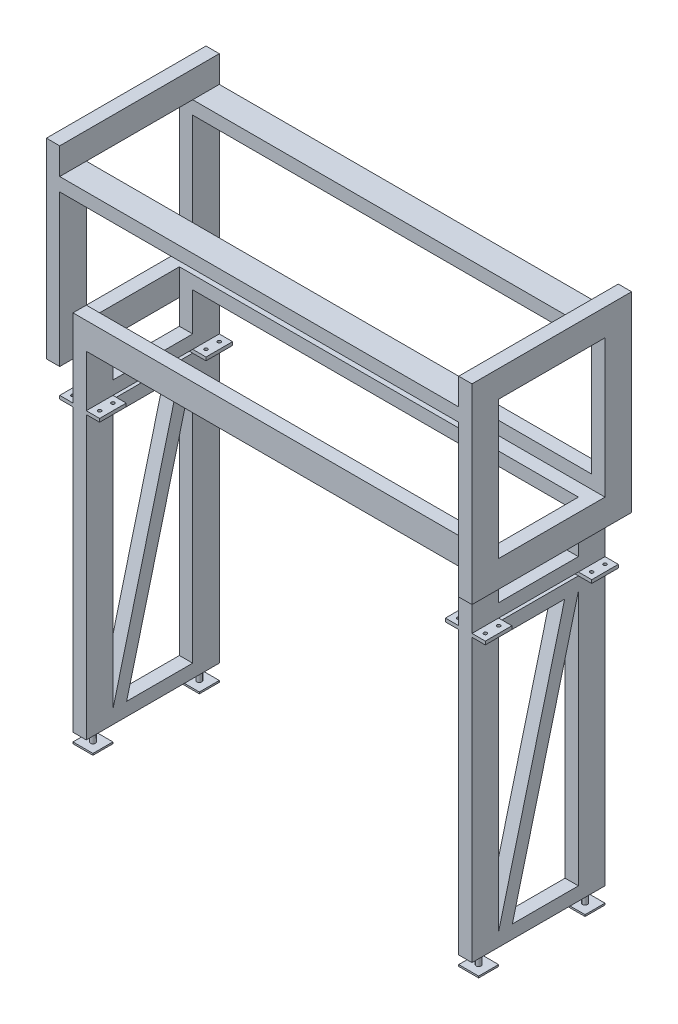
SolidWorks part; units mm, degrees
ref_plane "Front Plane" through (0, 0, 0) normal (0, 0, 1) x (1, 0, 0)
ref_plane "Top Plane" through (0, 0, 0) normal (0, 1, 0) x (1, 0, 0)
ref_plane "Right Plane" through (0, 0, 0) normal (1, 0, 0) x (0, 0, -1)
ref_plane "Plane1" through (-762, 0, 0) normal (1, 0, 0) x (0, 0, -1)
ref_plane "Plane2" through (762, 0, 0) normal (1, 0, 0) x (0, 0, -1)
sketch "Sketch1" plane through (-762, 0, 0) normal (1, 0, 0) x (0, 0, -1)
  line L1 (-203.2, 0) -> (203.2, 0)
  line L2 (-203.2, 0) -> (-203.2, 527.05)
  line L3 (-203.2, 527.05) -> (203.2, 527.05)
  line L4 (203.2, 0) -> (203.2, 527.05)
  line L5 (-304.8, 628.65) -> (304.8, 628.65)
  line L6 (-304.8, 628.65) -> (-304.8, -101.6)
  line L7 (-304.8, -101.6) -> (304.8, -101.6)
  line L8 (304.8, 628.65) -> (304.8, -101.6)
  point P4 (0, 0)
  point P10 (0, -101.6)
  dimension "D1" = 406.4
  dimension "D2" = 527.05
  dimension "D3" = 101.6
  dimension "D4" = 101.6
  dimension "D5" = 101.6
sketch "Sketch2" plane through (-762, 0, 0) normal (1, 0, 0) x (0, 0, -1)
  line L0 (-203.2, 50.8) -> (-203.2, 0)
  line L1 (-254, 50.8) -> (-203.2, 50.8)
  line L2 (-254, 50.8) -> (-254, -50.8)
  line L3 (-254, -50.8) -> (-152.4, -50.8)
  line L4 (-152.4, 0) -> (-152.4, -50.8)
  line L5 (-203.2, 0) -> (-152.4, 0)
  line L6 (203.2, 50.8) -> (203.2, 0)
  line L7 (254, -50.8) -> (152.4, -50.8)
  line L8 (254, -50.8) -> (254, 50.8)
  line L9 (254, 50.8) -> (203.2, 50.8)
  line L10 (152.4, -50.8) -> (152.4, 0)
  line L11 (203.2, 0) -> (152.4, 0)
  line L12 (-304.8, 628.65) -> (-304.8, -101.6) construction
  line L13 (-203.2, 527.05) -> (-304.8, 527.05)
  line L14 (-203.2, 527.05) -> (-203.2, 476.25)
  line L15 (-203.2, 476.25) -> (-304.8, 476.25)
  line L16 (-304.8, 527.05) -> (-304.8, 476.25)
  line L17 (304.8, 628.65) -> (304.8, -101.6) construction
  line L18 (203.2, 527.05) -> (304.8, 527.05)
  line L19 (203.2, 527.05) -> (203.2, 476.25)
  line L20 (203.2, 476.25) -> (304.8, 476.25)
  line L21 (304.8, 527.05) -> (304.8, 476.25)
  dimension "D1" = 50.8
  dimension "D2" = 101.6
  dimension "D3" = 50.8
  dimension "D4" = 101.6
  dimension "D5" = 50.8
  dimension "D6" = 50.8
sketch "Sketch3" plane through (-762, 0, 0) normal (1, 0, 0) x (0, 0, -1)
  line L0 (-152.4, 0) -> (-152.4, -50.8) construction
  line L1 (-254, -50.8) -> (-152.4, -50.8)
  line L2 (-254, -50.8) -> (-254, -1336.675)
  line L3 (-254, -1336.675) -> (-152.4, -1336.675)
  line L4 (-152.4, -50.8) -> (-152.4, -1336.675)
  line L5 (254, -50.8) -> (152.4, -50.8)
  line L6 (254, -50.8) -> (254, -1336.675)
  line L7 (254, -1336.675) -> (152.4, -1336.675)
  line L8 (152.4, -50.8) -> (152.4, -1336.675)
  line L9 (152.4, -50.8) -> (152.4, 0) construction
  line L10 (-254, -254) -> (254, -254) construction
  line L11 (-152.4, -1336.675) -> (152.4, -1336.675)
  line L12 (-152.4, -1336.675) -> (-152.4, -1285.875)
  line L13 (-152.4, -1285.875) -> (152.4, -1285.875)
  line L14 (152.4, -1336.675) -> (152.4, -1285.875)
  line L15 (-152.4, -247.65) -> (152.4, -247.65)
  line L16 (-152.4, -260.35) -> (152.4, -260.35)
  line L17 (-152.4, -196.85) -> (152.4, -196.85)
  line L18 (-152.4, -311.15) -> (152.4, -311.15)
  line L19 (152.4, -311.15) -> (-99.9255, -1285.875)
  line L20 (99.9255, -311.15) -> (-152.4, -1285.875)
  dimension "D1" = 1285.875
  dimension "D2" = 50.8
  dimension "D3" = 203.2
  dimension "D4" = 6.35
  dimension "D5" = 6.35
  dimension "D6" = 50.8
  dimension "D7" = 50.8
  dimension "D8" = 50.8
sketch "Sketch4" plane through (-762, 0, 0) normal (1, 0, 0) x (0, 0, -1)
  line L0 (-152.4, -50.8) -> (-152.4, -1336.675) construction
  line L1 (-254, -247.65) -> (-152.4, -247.65)
  line L2 (-254, -247.65) -> (-254, -260.35)
  line L3 (-254, -260.35) -> (-152.4, -260.35)
  line L4 (-152.4, -247.65) -> (-152.4, -260.35)
  line L5 (-152.4, -260.35) -> (152.4, -260.35) construction
  line L6 (-152.4, -247.65) -> (152.4, -247.65) construction
  line L7 (152.4, -247.65) -> (254, -247.65)
  line L8 (152.4, -247.65) -> (152.4, -260.35)
  line L9 (152.4, -260.35) -> (254, -260.35)
  line L10 (254, -247.65) -> (254, -260.35)
  line L11 (152.4, -50.8) -> (152.4, -1336.675) construction
  point P4 (-254, -254)
  point P14 (254, -254)
sketch "Sketch5" plane through (762, 0, 0) normal (1, 0, 0) x (0, 0, -1)
  line L1 (-203.2, 0) -> (203.2, 0)
  line L2 (-203.2, 0) -> (-203.2, 527.05)
  line L3 (-203.2, 527.05) -> (203.2, 527.05)
  line L4 (203.2, 0) -> (203.2, 527.05)
  line L5 (-304.8, 628.65) -> (304.8, 628.65)
  line L6 (-304.8, 628.65) -> (-304.8, -101.6)
  line L7 (-304.8, -101.6) -> (304.8, -101.6)
  line L8 (304.8, 628.65) -> (304.8, -101.6)
  point P4 (0, 0)
  point P10 (0, -101.6)
  dimension "D1" = 406.4
  dimension "D2" = 527.05
  dimension "D3" = 101.6
  dimension "D4" = 101.6
  dimension "D5" = 101.6
sketch "Sketch6" plane through (762, 0, 0) normal (1, 0, 0) x (0, 0, -1)
  line L0 (-203.2, 50.8) -> (-203.2, 0)
  line L1 (-254, 50.8) -> (-203.2, 50.8)
  line L2 (-254, 50.8) -> (-254, -50.8)
  line L3 (-254, -50.8) -> (-152.4, -50.8)
  line L4 (-152.4, 0) -> (-152.4, -50.8)
  line L5 (-203.2, 0) -> (-152.4, 0)
  line L6 (203.2, 50.8) -> (203.2, 0)
  line L7 (254, -50.8) -> (152.4, -50.8)
  line L8 (254, -50.8) -> (254, 50.8)
  line L9 (254, 50.8) -> (203.2, 50.8)
  line L10 (152.4, -50.8) -> (152.4, 0)
  line L11 (203.2, 0) -> (152.4, 0)
  line L13 (-203.2, 527.05) -> (-304.8, 527.05)
  line L14 (-203.2, 527.05) -> (-203.2, 476.25)
  line L15 (-203.2, 476.25) -> (-304.8, 476.25)
  line L16 (-304.8, 527.05) -> (-304.8, 476.25)
  line L17 (304.8, 628.65) -> (304.8, -101.6) construction
  line L18 (203.2, 527.05) -> (304.8, 527.05)
  line L19 (203.2, 527.05) -> (203.2, 476.25)
  line L20 (203.2, 476.25) -> (304.8, 476.25)
  line L21 (304.8, 527.05) -> (304.8, 476.25)
  line L23 (-304.8, 628.65) -> (-304.8, -101.6) construction
  point P8 (-227.0496, -20.0991)
  point P9 (0, 0)
  point P19 (220.3116, 515.0069)
  point P20 (0, 0)
  point P26 (223.0451, -13.1209)
  point P27 (0, 0)
  point P30 (-219.7332, 512.1395)
  point P31 (0, 0)
  dimension "D1" = 50.8
  dimension "D2" = 101.6
  dimension "D3" = 50.8
  dimension "D4" = 101.6
  dimension "D5" = 50.8
  dimension "D6" = 50.8
sketch "Sketch7" plane through (762, 0, 0) normal (1, 0, 0) x (0, 0, -1)
  line L1 (-254, -50.8) -> (-152.4, -50.8)
  line L2 (-254, -50.8) -> (-254, -1336.675)
  line L3 (-254, -1336.675) -> (-152.4, -1336.675)
  line L4 (-152.4, -50.8) -> (-152.4, -1336.675)
  line L5 (254, -50.8) -> (152.4, -50.8)
  line L6 (254, -50.8) -> (254, -1336.675)
  line L7 (254, -1336.675) -> (152.4, -1336.675)
  line L8 (152.4, -50.8) -> (152.4, -1336.675)
  line L10 (-254, -254) -> (254, -254) construction
  line L11 (-152.4, -1336.675) -> (152.4, -1336.675)
  line L12 (-152.4, -1336.675) -> (-152.4, -1285.875)
  line L13 (-152.4, -1285.875) -> (152.4, -1285.875)
  line L14 (152.4, -1336.675) -> (152.4, -1285.875)
  line L15 (-152.4, -247.65) -> (152.4, -247.65)
  line L16 (-152.4, -260.35) -> (152.4, -260.35)
  line L17 (-152.4, -196.85) -> (152.4, -196.85)
  line L18 (-152.4, -311.15) -> (152.4, -311.15)
  line L19 (152.4, -311.15) -> (-99.9255, -1285.875)
  line L20 (99.9255, -311.15) -> (-152.4, -1285.875)
  line L21 (-152.4, 0) -> (-152.4, -50.8) construction
  point P10 (-245.6724, -77.9499)
  point P11 (0, 0)
  point P12 (0, 0)
  point P30 (0, 0)
  point P32 (0, 0)
  point P34 (0, 0)
  dimension "D1" = 1285.875
  dimension "D2" = 50.8
  dimension "D3" = 203.2
  dimension "D4" = 6.35
  dimension "D5" = 6.35
  dimension "D6" = 50.8
  dimension "D7" = 50.8
  dimension "D8" = 50.8
sketch "Sketch8" plane through (762, 0, 0) normal (1, 0, 0) x (0, 0, -1)
  line L1 (-254, -247.65) -> (-152.4, -247.65)
  line L2 (-254, -247.65) -> (-254, -260.35)
  line L3 (-254, -260.35) -> (-152.4, -260.35)
  line L4 (-152.4, -247.65) -> (-152.4, -260.35)
  line L7 (152.4, -247.65) -> (254, -247.65)
  line L8 (152.4, -247.65) -> (152.4, -260.35)
  line L9 (152.4, -260.35) -> (254, -260.35)
  line L10 (254, -247.65) -> (254, -260.35)
  line L12 (-152.4, -50.8) -> (-152.4, -1336.675) construction
  line L13 (-152.4, -247.65) -> (152.4, -247.65) construction
  line L14 (152.4, -50.8) -> (152.4, -1336.675) construction
  point P4 (-254, -254)
  point P6 (-280.1492, -246.8881)
  point P14 (254, -254)
  point P17 (277.2789, -248.7525)
extrude "Boss-Extrude1" add sketch "Sketch1" against normal blind 50.8
extrude "Boss-Extrude2" add sketch "Sketch2" along normal blind 1524
extrude "Boss-Extrude3" add sketch "Sketch3" along normal blind 50.8 contours L2 L10 L4 L1 | L17 L4 L15 L8 | L8 L10 L6 L5 | L4 L18 L8 L16 | L10 L2 L3 L4 | L10 L8 L7 L6 | L18 L20 L13 L19 | L13 L4 L11 L8 region at (-762, -152.4, 203.2) region at (-762, -795.3375, 203.2) region at (-762, -222.25, 0) region at (-762, -152.4, -203.2) region at (-762, -1311.275, 0) region at (-762, -285.75, 0) region at (-762, -795.3375, -203.2) region at (-762, -798.5125, 0)
extrude "Boss-Extrude4" add sketch "Sketch4" along normal blind 101.6
extrude "Boss-Extrude5" add sketch "Sketch4<2>" against normal blind 50.8
sketch "Sketch4<2>" plane through (-762, 0, 0) normal (1, 0, 0) x (0, 0, -1) same geometry as "Sketch4"
extrude "Boss-Extrude6" add sketch "Sketch5" along normal blind 50.8
extrude "Boss-Extrude7" add sketch "Sketch7" against normal blind 50.8 contours L2 L10 L4 L1 | L17 L4 L15 L8 | L8 L10 L6 L5 | L10 L8 L7 L6 | L4 L18 L8 L16 | L10 L2 L3 L4 | L18 L20 L13 L19 | L13 L4 L11 L8 region at (762, -152.4, 203.2) region at (762, -795.3375, 203.2) region at (762, -222.25, 0) region at (762, -152.4, -203.2) region at (762, -1311.275, 0) region at (762, -285.75, 0) region at (762, -795.3375, -203.2) region at (762, -798.5125, 0)
extrude "Boss-Extrude8" add sketch "Sketch8" along normal blind 50.8
extrude "Boss-Extrude9" add sketch "Sketch8<2>" against normal blind 101.6
sketch "Sketch8<2>" plane through (762, 0, 0) normal (1, 0, 0) x (0, 0, -1) same geometry as "Sketch8"
ref_plane "Plane3" through (0, -247.65, 0) normal (0, 1, 0) x (1, 0, 0)
sketch "Sketch9" plane through (0, -247.65, 0) normal (0, 1, 0) x (1, 0, 0)
  line L0 (-660.4, 254) -> (-660.4, 152.4) construction
  line L1 (-660.4, 254) -> (-711.2, 254) construction
  line L2 (-711.2, 152.4) -> (-711.2, 254) construction
  line L3 (-660.4, 152.4) -> (-711.2, 152.4) construction
  line L4 (-812.8, 152.4) -> (-762, 152.4) construction
  line L5 (-812.8, 254) -> (-812.8, 152.4) construction
  line L6 (-812.8, 254) -> (-762, 254) construction
  line L7 (-762, 254) -> (-762, 152.4) construction
  line L8 (-660.4, -152.4) -> (-711.2, -152.4) construction
  line L9 (-660.4, -152.4) -> (-660.4, -254) construction
  line L10 (-660.4, -254) -> (-711.2, -254) construction
  line L11 (-711.2, -254) -> (-711.2, -152.4) construction
  line L12 (-812.8, -254) -> (-762, -254) construction
  line L13 (-812.8, -152.4) -> (-812.8, -254) construction
  line L14 (-812.8, -152.4) -> (-762, -152.4) construction
  line L15 (-762, -152.4) -> (-762, -254) construction
  line L16 (660.4, 152.4) -> (711.2, 152.4) construction
  line L17 (711.2, 254) -> (711.2, 152.4) construction
  line L18 (660.4, 254) -> (660.4, 152.4) construction
  line L19 (660.4, 254) -> (711.2, 254) construction
  line L20 (812.8, 254) -> (762, 254) construction
  line L21 (812.8, 254) -> (812.8, 152.4) construction
  line L22 (812.8, 152.4) -> (762, 152.4) construction
  line L23 (762, 254) -> (762, 152.4) construction
  line L24 (660.4, -254) -> (711.2, -254) construction
  line L25 (660.4, -152.4) -> (660.4, -254) construction
  line L26 (660.4, -152.4) -> (711.2, -152.4) construction
  line L27 (711.2, -152.4) -> (711.2, -254) construction
  line L28 (812.8, -152.4) -> (762, -152.4) construction
  line L29 (812.8, -152.4) -> (812.8, -254) construction
  line L30 (812.8, -254) -> (762, -254) construction
  line L31 (762, -152.4) -> (762, -254) construction
  line L32 (-660.4, 254) -> (-660.4, 152.4)
  line L33 (-660.4, 254) -> (-711.2, 254)
  line L34 (-711.2, 152.4) -> (-711.2, 254)
  line L35 (-660.4, 152.4) -> (-711.2, 152.4)
  line L36 (-812.8, 152.4) -> (-762, 152.4)
  line L37 (-812.8, 254) -> (-812.8, 152.4)
  line L38 (-812.8, 254) -> (-762, 254)
  line L39 (-762, 254) -> (-762, 152.4)
  line L40 (-660.4, -152.4) -> (-711.2, -152.4)
  line L41 (-660.4, -152.4) -> (-660.4, -254)
  line L42 (-660.4, -254) -> (-711.2, -254)
  line L43 (-711.2, -254) -> (-711.2, -152.4)
  line L44 (-812.8, -254) -> (-762, -254)
  line L45 (-812.8, -152.4) -> (-812.8, -254)
  line L46 (-812.8, -152.4) -> (-762, -152.4)
  line L47 (-762, -152.4) -> (-762, -254)
  line L48 (660.4, 152.4) -> (711.2, 152.4)
  line L49 (711.2, 254) -> (711.2, 152.4)
  line L50 (660.4, 254) -> (660.4, 152.4)
  line L51 (660.4, 254) -> (711.2, 254)
  line L52 (812.8, 254) -> (762, 254)
  line L53 (812.8, 254) -> (812.8, 152.4)
  line L54 (812.8, 152.4) -> (762, 152.4)
  line L55 (762, 254) -> (762, 152.4)
  line L56 (660.4, -254) -> (711.2, -254)
  line L57 (660.4, -152.4) -> (660.4, -254)
  line L58 (660.4, -152.4) -> (711.2, -152.4)
  line L59 (711.2, -152.4) -> (711.2, -254)
  line L60 (812.8, -152.4) -> (762, -152.4)
  line L61 (812.8, -152.4) -> (812.8, -254)
  line L62 (812.8, -254) -> (762, -254)
  line L63 (762, -152.4) -> (762, -254)
  circle A0 centre (-787.4, 228.6) radius 6.35
  circle A1 centre (-787.4, 177.8) radius 6.35
  circle A2 centre (-685.8, 177.8) radius 6.35
  circle A3 centre (-685.8, 228.6) radius 6.35
  circle A4 centre (-787.4, -177.8) radius 6.35
  circle A5 centre (-787.4, -228.6) radius 6.35
  circle A6 centre (-685.8, -177.8) radius 6.35
  circle A7 centre (-685.8, -228.6) radius 6.35
  circle A8 centre (685.8, 228.6) radius 6.35
  circle A9 centre (685.8, 177.8) radius 6.35
  circle A10 centre (787.4, 228.6) radius 6.35
  circle A11 centre (787.4, 177.8) radius 6.35
  circle A12 centre (685.8, -177.8) radius 6.35
  circle A13 centre (685.8, -228.6) radius 6.35
  circle A14 centre (787.4, -177.8) radius 6.35
  circle A15 centre (787.4, -228.6) radius 6.35
  point P35 (-787.4, 254)
  point P42 (-685.8, 254)
  point P43 (-787.4, -152.4)
  point P53 (-685.8, -152.4)
  point P68 (0, 0)
  point P69 (685.8, 254)
  point P70 (0, 0)
  point P71 (787.4, 254)
  point P72 (0, 0)
  point P73 (0, 0)
  point P74 (787.4, -152.4)
  point P75 (685.8, -152.4)
  point P76 (0, 0)
  dimension "D2" = 12.7
  dimension "D6" = 12.7
  dimension "D9" = 12.7
  dimension "D11" = 12.7
  dimension "D1" = 25.4
  dimension "D3" = 50.8
  dimension "D4" = 25.4
  dimension "D5" = 50.8
  dimension "D7" = 25.4
  dimension "D8" = 50.8
  dimension "D10" = 25.4
  dimension "D12" = 50.8
extrude "Cut-Extrude1" cut sketch "Sketch9" against normal blind 12.7 contours A1 | A0 | A3 | A2 | A4 | A5 | A6 | A7 | A12 | A13 | A14 | A15 | A8 | A9 | A10 | A11 region at (-787.4, -247.65, -228.6) region at (-787.4, -247.65, -177.8) region at (-685.8, -247.65, -177.8) region at (-685.8, -247.65, -228.6) region at (-787.4, -247.65, 177.8) region at (-787.4, -247.65, 228.6) region at (-685.8, -247.65, 177.8) region at (-685.8, -247.65, 228.6) region at (685.8, -247.65, -228.6) region at (685.8, -247.65, -177.8) region at (787.4, -247.65, -228.6) region at (787.4, -247.65, -177.8) region at (685.8, -247.65, 177.8) region at (685.8, -247.65, 228.6) region at (787.4, -247.65, 177.8) region at (787.4, -247.65, 228.6)
ref_plane "Plane4" through (0, -1387.475, 0) normal (0, -1, 0) x (-1, 0, 0)
sketch "Sketch10" plane through (0, -1387.475, 0) normal (0, -1, 0) x (-1, 0, 0)
  line L0 (711.2, -254) -> (762, -254) construction
  line L1 (-698.5, -241.3) -> (-774.7, -241.3)
  line L2 (774.7, -241.3) -> (698.5, -241.3)
  line L3 (774.7, -241.3) -> (774.7, -165.1)
  line L4 (774.7, -165.1) -> (698.5, -165.1)
  line L5 (698.5, -241.3) -> (698.5, -165.1)
  line L6 (-698.5, -241.3) -> (-698.5, -165.1)
  line L7 (-698.5, -165.1) -> (-774.7, -165.1)
  line L8 (-774.7, -241.3) -> (-774.7, -165.1)
  line L9 (-698.5, 165.1) -> (-774.7, 165.1)
  line L10 (-698.5, 165.1) -> (-698.5, 241.3)
  line L11 (-698.5, 241.3) -> (-774.7, 241.3)
  line L12 (-774.7, 165.1) -> (-774.7, 241.3)
  line L13 (774.7, 165.1) -> (698.5, 165.1)
  line L14 (774.7, 165.1) -> (774.7, 241.3)
  line L15 (774.7, 241.3) -> (698.5, 241.3)
  line L16 (698.5, 165.1) -> (698.5, 241.3)
  line L17 (774.7, -241.3) -> (-698.5, -241.3) construction
  line L18 (774.7, -241.3) -> (774.7, 165.1) construction
  circle A0 centre (736.6, -203.2) radius 9.525
  circle A1 centre (-736.6, -203.2) radius 9.525
  circle A2 centre (-736.6, 203.2) radius 9.525
  circle A3 centre (736.6, 203.2) radius 9.525
  point P2 (736.6, -241.3)
  point P5 (736.6, -254)
  point P10 (698.5, -203.2)
  point P11 (0, 0)
  dimension "D1" = 19.05
  dimension "D2" = 50.8
  dimension "D3" = 76.2
  dimension "D6" = 1473.2
  dimension "D7" = 406.4
  dimension "D4" = 2
  dimension "D5" = 2
extrude "Boss-Extrude10" add sketch "Sketch10" against normal blind 50.8 contours A0 | A3 | A1 | A2 region at (-736.6, -1387.475, 203.2) region at (736.6, -1387.475, 203.2) region at (736.6, -1387.475, -203.2) region at (-736.6, -1387.475, -203.2)
extrude "Boss-Extrude11" add sketch "Sketch10<3>" against normal blind 6.35
sketch "Sketch10<3>" plane through (0, -1387.475, 0) normal (0, -1, 0) x (-1, 0, 0) same geometry as "Sketch10"
